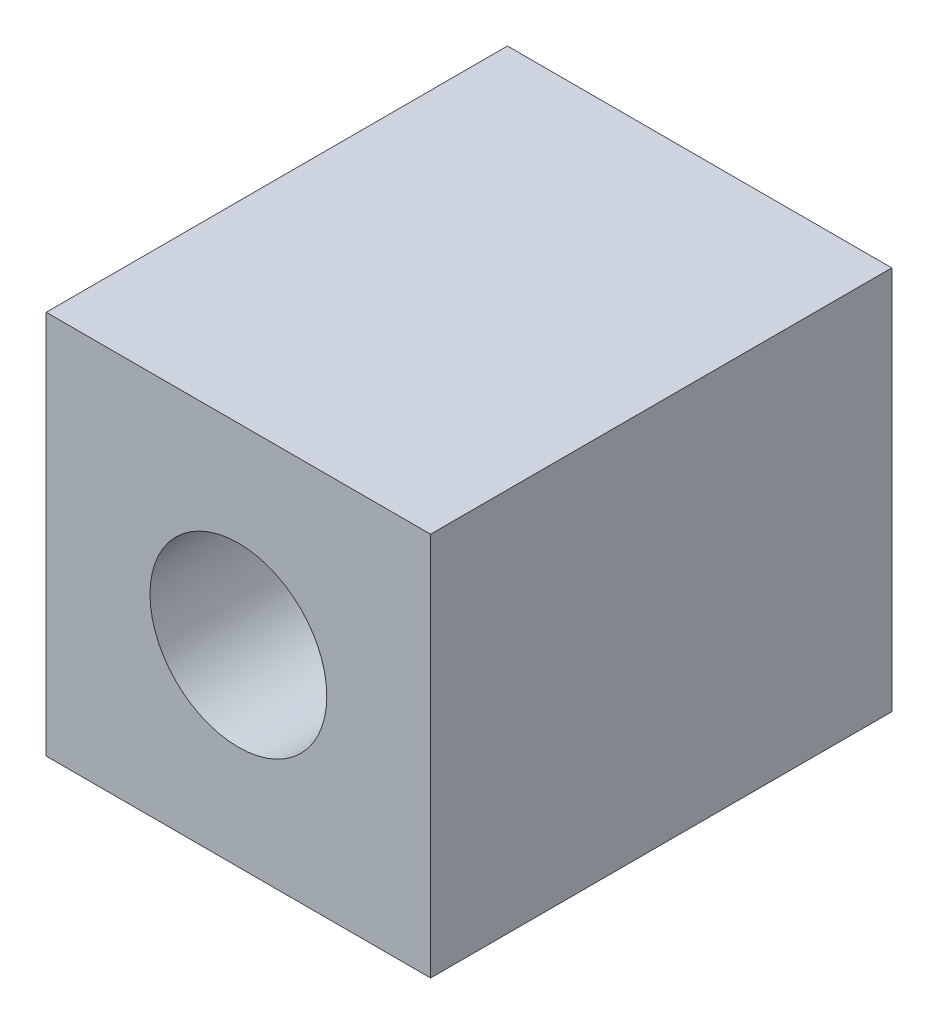
SolidWorks part; units mm, degrees
ref_plane "正面" through (0, 0, 0) normal (0, 0, 1) x (1, 0, 0)
ref_plane "平面" through (0, 0, 0) normal (0, 1, 0) x (1, 0, 0)
ref_plane "右側面" through (0, 0, 0) normal (1, 0, 0) x (0, 0, -1)
sketch "ｽｹｯﾁ1" plane through (0, 0, 0) normal (0, 0, 1) x (1, 0, 0)
  line L1 (-2.7788, 2.893) -> (2.2212, 2.893)
  line L2 (-2.7788, 2.893) -> (-2.7788, -2.107)
  line L3 (-2.7788, -2.107) -> (2.2212, -2.107)
  line L4 (2.2212, 2.893) -> (2.2212, -2.107)
  dimension "D1" = 5
  dimension "D2" = 5
extrude "ﾎﾞｽ - 押し出し1" add sketch "ｽｹｯﾁ1" along normal blind 6
sketch "ｽｹｯﾁ2" plane through (0, 0, 6) normal (0, 0, 1) x (1, 0, 0)
  line L0 (2.2212, 2.893) -> (-2.7788, 2.893) construction
  line L1 (-2.7788, 2.893) -> (-2.7788, -2.107) construction
  circle A0 centre (-0.2788, 0.393) radius 1.15
  dimension "D1" = 2.3
  dimension "D2" = 2.5
  dimension "D3" = 2.5
extrude "ｶｯﾄ - 押し出し1" cut sketch "ｽｹｯﾁ2" against normal through all
